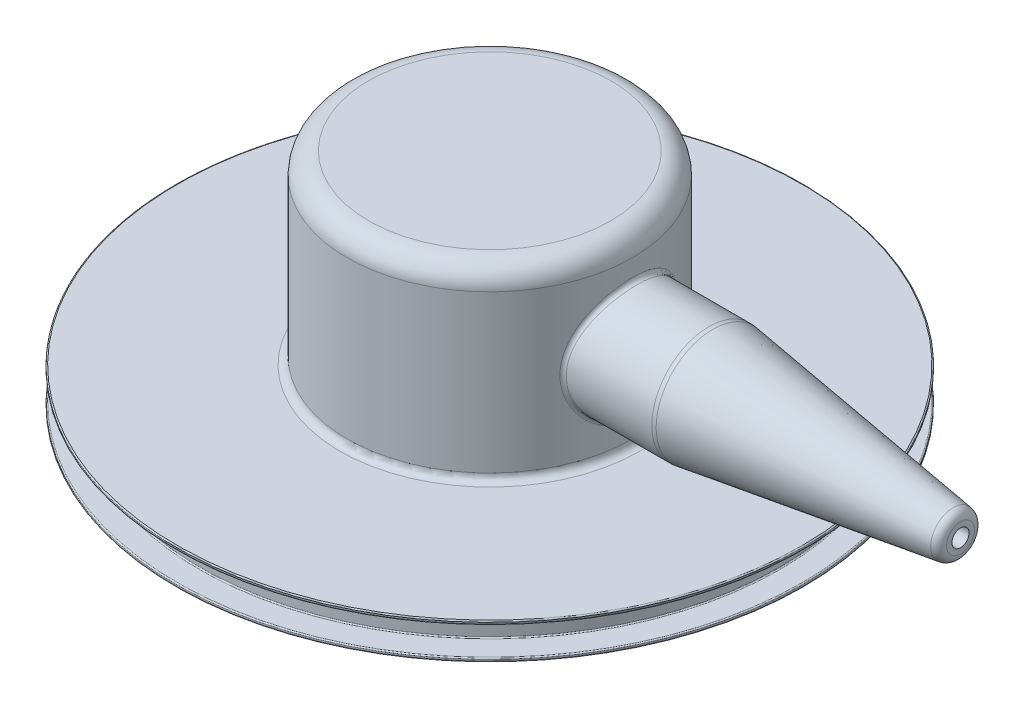
SolidWorks part; units mm, degrees
ref_plane "front" through (0, 0, 0) normal (0, 0, 1) x (1, 0, 0)
ref_plane "top" through (0, 0, 0) normal (0, 1, 0) x (1, 0, 0)
ref_plane "right" through (0, 0, 0) normal (1, 0, 0) x (0, 0, -1)
sketch "Sketch1" plane through (0, 0, 0) normal (0, 0, 1) x (1, 0, 0)
  line L0 (0, 16) -> (0, 0)
  line L13 (0, 16) -> (10, 16)
  line L20 (0, 0) -> (19, 0)
  line L21 (19, 0) -> (22, 0.5)
  line L22 (22, 0.5) -> (22, 0.75)
  line L23 (22, 0.75) -> (20.2748, 0.75)
  line L24 (20.2748, 0.75) -> (20.2748, 2.75)
  line L25 (20.2748, 2.75) -> (22, 2.75)
  line L26 (22, 2.75) -> (22, 3)
  line L27 (10, 16) -> (10, 3)
  line L28 (10, 3) -> (22, 3)
  point P2 (20.2748, 2.75)
  point P4 (19, 0)
  point P7 (22, 0.75)
  point P10 (22, 0.5)
  point P12 (22, 0)
  point P13 (0, 0)
  point P16 (22, 3)
  dimension "D1" = 10
  dimension "D2" = 3
  dimension "D3" = 3
  dimension "D4" = 0.25
  dimension "D5" = 0.25
  dimension "D6" = 0.5
  dimension "D7" = 16
revolve "Revolve1" add sketch "Sketch1" angle 360 about L0
sketch "Sketch3" plane through (0, 0, 0) normal (1, 0, 0) x (0, 0, -1)
  line L0 (0, 0) -> (0, 64.7736) construction
  circle A0 centre (0, 9) radius 4
  circle A1 centre (0, 9) radius 3
  dimension "D1" = 9
  dimension "D2" = 8
  dimension "D3" = 6
extrude "Boss-Extrude1" add sketch "Sketch3" along normal blind 25 contours A0
extrude "Boss-Extrude2" add sketch "Sketch3<5>" along normal blind 8 from surface contours A1 starting at face at (25, 9, -4)
sketch "Sketch3<5>" plane through (0, 0, 0) normal (1, 0, 0) x (0, 0, -1) same geometry as "Sketch3"
sketch "Sketch11" plane through (0, 0, 0) normal (0, 0, 1) x (1, 0, 0)
  line L0 (0, 4) -> (0, 0)
  line L2 (0, 0) -> (19, 0)
  line L4 (0, 0) -> (0, 4.7847) construction
  arc A1 (0, 4) -> (19, 0) centre (-0.6724, -46.3191) cw
  dimension "D1" = 4
  dimension "D2" = 19
revolve "Cut-Revolve10" cut sketch "Sketch11" angle 360 about L4
sketch "Sketch15" plane through (0, 0, 0) normal (0, 1, 0) x (1, 0, 0)
  circle A0 centre (0, 0) radius 1.8
extrude "Cut-Extrude1" cut sketch "Sketch15" along normal blind 11.8 and the other way through all
sketch "Sketch16" plane through (0, 0, 0) normal (0, 0, 1) x (1, 0, 0)
  line L0 (33, 12) -> (33, 13.5)
  line L1 (33, 6) -> (33, 12) construction
  line L3 (25, 5) -> (25, 13) construction
  line L5 (33, 9) -> (25, 9) construction
  line L7 (25, 13) -> (10, 13) construction
  line L8 (15.5034, 13) -> (33, 13.5)
  line L9 (15.5034, 13) -> (33, 13)
  line L10 (33, 13) -> (33, 12)
sketch "Sketch19" plane through (0, 0, 0) normal (0, 0, 1) x (1, 0, 0)
  line L0 (25, 13) -> (10, 13) construction
  line L1 (33, 13) -> (15.5, 13)
  line L2 (33, 13) -> (33, 10.5)
  line L3 (15.5, 13) -> (33, 10.5)
  line L4 (33, 9) -> (44.2045, 9) construction
  point P0 (33, 12)
  point P1 (25, 13)
  point P3 (33, 13)
  point P5 (15.5, 13)
  point P6 (33, 9)
  dimension "D1" = 17.5
  dimension "D2" = 2.5
  dimension "D3" = 4
revolve "Cut-Revolve14" cut sketch "Sketch19" angle 360 about L4
sketch "Sketch17" plane through (0, 0, 0) normal (0, 0, 1) x (1, 0, 0)
  line L1 (33, 9.6) -> (33, 9)
  line L4 (33, 9) -> (0, 9)
  line L13 (15.5034, 11.8) -> (0, 11.8)
  line L14 (0, 11.8) -> (0, 9)
  line L15 (15.5034, 11.8) -> (30.9004, 9.6)
  line L18 (33, 9.6) -> (30.9004, 9.6)
  dimension "D1" = 30.9004
  dimension "D2" = 9.6
  dimension "D3" = 11.8
  dimension "D4" = 33
  dimension "D5" = 9
revolve "Cut-Revolve13" cut sketch "Sketch17" angle 360 about L4
fillet "Fillet1" radius 0.5 1 edges at (-10, 3, 0)
fillet "Fillet2" radius 0.3 1 edges at (9.184, 9.5886, -3.9565)
fillet "Fillet3" radius 2 1 edges at (15.5, 9, 4)
fillet "Fillet4" radius 1.5 1 edges at (-10, 16, 0)
fillet "Fillet5" radius 0.5 1 edges at (0, 0, -19)
fillet "Fillet6" radius 0.08 6 edges at (-20.2748, 2.75, 0) (-20.2748, 0.75, 0) (-22, 0.5, 0) (-22, 0.75, 0) (-22, 2.75, 0) (-22, 3, 0)
fillet "Fillet7" radius 0.08 1 edges at (0, 3.9437, -1.8)
fillet "Fillet8" radius 0.6 1 edges at (33, 9, 1.5)
